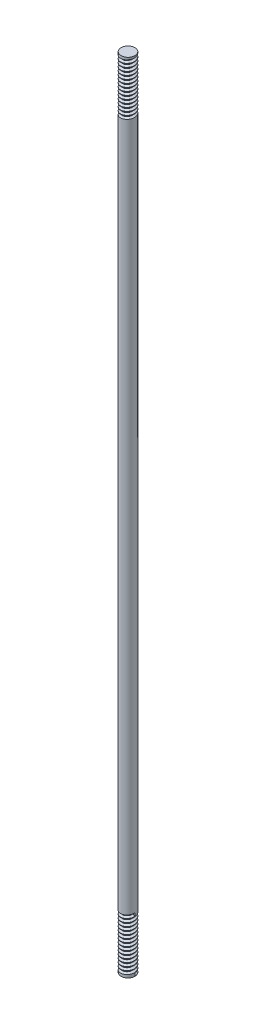
SolidWorks part; units mm, degrees
ref_plane "Piano frontale" through (0, 0, 0) normal (0, 0, 1) x (1, 0, 0)
ref_plane "Piano superiore" through (0, 0, 0) normal (0, 1, 0) x (1, 0, 0)
ref_plane "Piano destro" through (0, 0, 0) normal (1, 0, 0) x (0, 0, -1)
sketch "Schizzo1" plane through (0, 0, 0) normal (0, 1, 0) x (1, 0, 0)
  circle A0 centre (0, 0) radius 3
  dimension "D1" = 6
extrude "Estrusione-Estrusione1" add sketch "Schizzo1" along normal blind 345
thread "Filettatura1" pitch 1.5 method cut profile "Profilo filettatura1" start angle 0, offset 0, length 0, pitch 1.5, diameter 6
ref_plane "Piano1" through (-3, 345, 0) normal (0, 0, 1) x (-1, 0, 0)
sketch "Profilo filettatura1" plane through (-3, 345, 0) normal (0, 0, 1) x (-1, 0, 0)
  line L0 (0, 0) -> (0, 1.5) construction
  line L11 (0, 0) -> (0, 1.3125)
  line L12 (0, 1.3125) -> (-0.8119, 0.8437)
  line L13 (-0.8119, 0.8437) -> (-0.8119, 0.4687)
  line L15 (-0.8119, 0.4687) -> (0, 0)
  line L17 (-0.8119, 0.6562) -> (0, 0.6562) construction
  point P2 (0, 0)
  dimension "Pitch" = 1.5
  dimension "Profile_Angle" = 60
  dimension "Profile_Land" = 0.375
  dimension "Profile_Height" = 0.8119
thread "Filettatura2" pitch 1.5 method cut profile "Profilo filettatura2" start angle 0, offset 0, length 0, pitch 1.5, diameter 6
ref_plane "Piano2" through (3, 0, 0) normal (0, 0, 1) x (1, 0, 0)
sketch "Profilo filettatura2" plane through (3, 0, 0) normal (0, 0, 1) x (1, 0, 0)
  line L0 (0, 0) -> (0, 1.5) construction
  line L11 (0, 0) -> (0, 1.3125)
  line L12 (0, 1.3125) -> (-0.8119, 0.8437)
  line L13 (-0.8119, 0.8437) -> (-0.8119, 0.4687)
  line L15 (-0.8119, 0.4687) -> (0, 0)
  line L17 (-0.8119, 0.6562) -> (0, 0.6562) construction
  point P2 (0, 0)
  dimension "Pitch" = 1.5
  dimension "Profile_Angle" = 60
  dimension "Profile_Land" = 0.375
  dimension "Profile_Height" = 0.8119
